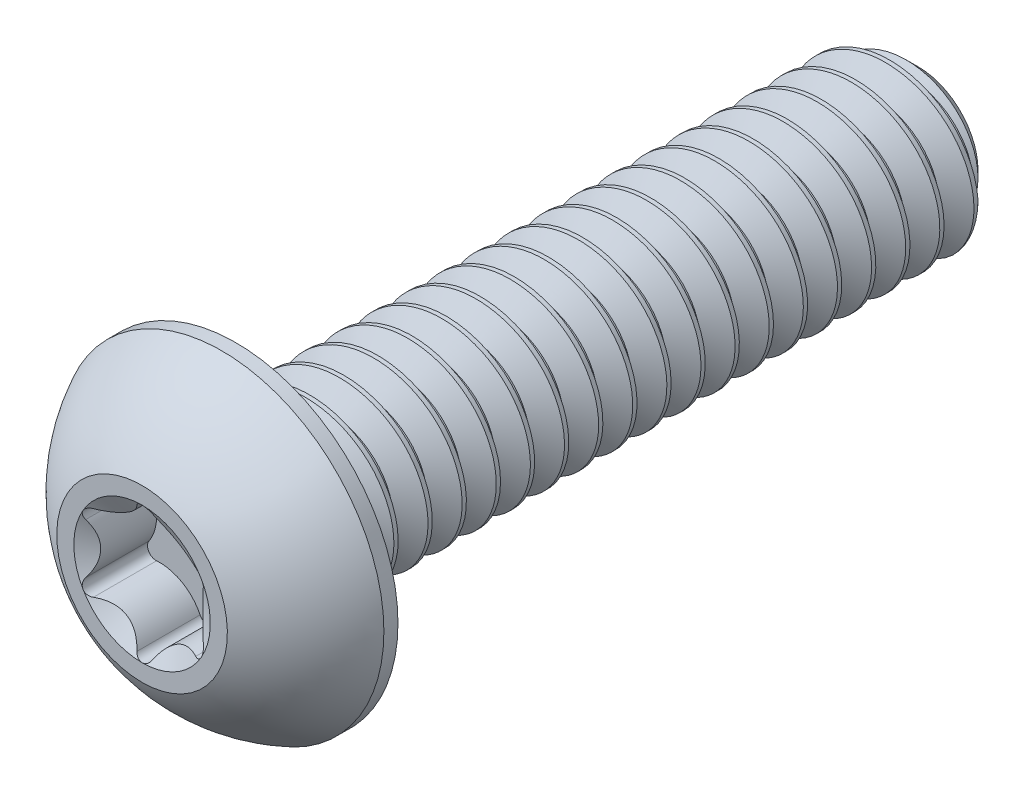
SolidWorks part; units mm, degrees
ref_plane "Front" through (0, 0, 0) normal (0, 0, 1) x (1, 0, 0)
ref_plane "Top" through (0, 0, 0) normal (0, 1, 0) x (1, 0, 0)
ref_plane "Right" through (0, 0, 0) normal (1, 0, 0) x (0, 0, -1)
sketch "Sketch1" plane through (0, 0, 0) normal (1, 0, 0) x (0, 0, -1)
  line L2 (1.1, 1) -> (9.1, 1)
  line L3 (9.1, 1) -> (9.1, 0)
  line L4 (9.1, 0) -> (1.1, 0)
  line L6 (0.935, 1.9) -> (1.1, 1.9) construction
  line L7 (9.1, 1) -> (9.1, -1) construction
  line L8 (0, 0) -> (1.1, 0) construction
  line L9 (1.1, 1.9) -> (1.1, -1.9) construction
  line L11 (1.1, 1) -> (1.1, 0)
  line L14 (0, 0) -> (0, 1) construction
  arc A3 (0, 1) -> (0.935, 1.9) centre (1.8632, 0) cw construction
  dimension "D1" = 0.165
revolve "Revolve1" add sketch "Sketch1" angle 360 mid plane about L4
sketch "Sketch3" plane through (0, 0, -9.1) normal (0, 0, -1) x (-1, 0, 0)
  circle A0 centre (0, 0) radius 1
curve "Helix/Spiral1" pitch 0.4 height 8.4 radius 1 centre (0, 0, -9.1) axis (0, 0, 1) start towards (0, 1, 0)
sketch "Sketch2" plane through (0, 0, 0) normal (1, 0, 0) x (0, 0, -1)
  line L0 (9.1, 1) -> (9.45, 1)
  line L1 (9.45, 1) -> (9.3, 0.7402)
  line L2 (9.3, 0.7402) -> (9.25, 0.7402)
  line L3 (9.25, 0.7402) -> (9.1, 1)
  line L4 (9.175, 0.8701) -> (9.375, 0.8701) construction
  dimension "D1" = 60
  dimension "D2" = 0.05
  dimension "D3" = 0.2
chamfer "Chamfer1" distance 0.3 angle 45 1 edges at (0, 1, -9.1)
sweep "Cut-Sweep1" cut profiles "Sketch2" path "Helix/Spiral1" align with end faces yes
sketch "Sketch7" plane through (0, 0, 0) normal (1, 0, 0) x (0, 0, -1)
  line L0 (0, 0) -> (0, 1) construction
  line L6 (0.935, 1.9) -> (1.1, 1.9) construction
  line L8 (0, 0) -> (1.1, 0) construction
  line L11 (1.1, 1.9) -> (1.1, -1.9) construction
  line L12 (0.935, 1.9) -> (1.1, 1.9)
  line L13 (0, 0) -> (1.1, 0)
  line L15 (1.1, 1.9) -> (1.1, 0)
  line L16 (0, 1) -> (0, 0)
  arc A2 (0.935, 1.9) -> (0, 1) centre (1.8632, 0) ccw construction
  arc A3 (0.935, 1.9) -> (0, 1) centre (1.8632, 0) ccw
revolve "Revolve2" add sketch "Sketch7" angle 360 mid plane about L13
sketch "Sketch5" plane through (0, 0, 0) normal (0, 0, 1) x (1, 0, 0)
  line L0 (2.6125, 0) -> (-2.6125, 0) construction
  line L2 (0, 0) -> (-0.6928, 0.4)
  line L3 (0, 0) -> (-0.6928, -0.4)
  line L4 (0, 0.8) -> (0, 0.7) construction
  line L5 (0, 0.7) -> (0, 0.6) construction
  circle A0 centre (0, 0) radius 0.6 construction
  circle A1 centre (0, 0) radius 0.7 construction
  circle A2 centre (0, 0) radius 0.8 construction
  arc A3 (-0.6894, 0.2944) -> (-0.6894, -0.2944) centre (-1.1298, 0) cw
  arc A4 (-0.6894, 0.2944) -> (-0.6928, 0.4) centre (-0.6062, 0.35) cw
  arc A5 (-0.6894, -0.2944) -> (-0.6928, -0.4) centre (-0.6062, -0.35) ccw
  dimension "D4" = 1.2
  dimension "D2" = 1.6
  dimension "D1" = 30
extrude "Cut-Extrude2" cut sketch "Sketch5" against normal blind 0.77
pattern_circular "CirPattern1" count 6 over 360 of "Cut-Extrude2"
sketch "Sketch11" plane through (0, 0, 0) normal (0, 0, 1) x (1, 0, 0)
  circle A0 centre (0, 0) radius 0.8 construction
  circle A1 centre (0, 0) radius 0.8
extrude "Cut-Extrude3" cut sketch "Sketch11" against normal blind 0.77 draft 60
sketch "Sketch9" [suppressed] plane through (0, 0, -1.4986) normal (0, 0, 1) x (1, 0, 0)
  circle A2 centre (0, 0) radius 1.4224
extrude "Boss-Extrude2" [suppressed] add sketch "Sketch9" against normal offset from surface (7.0104 mm away) 31.75 up to face at (0, 0.7, -9.1)
sketch "Sketch10" plane through (0, 0, 0) normal (1, 0, 0) x (0, 0, -1)
  line L0 (9.1, 1) -> (9.1, -1) construction
  point P0 (8.5, -1)
  dimension "D1" = 0.6
equation "\"D3@Helix/Spiral1\" = \"Lg@Sketch1\" + \"D4@Helix/Spiral1\""
equation "\"D2@Sketch2\" = \"D4@Helix/Spiral1\" * .125"
equation "\"D3@Sketch2\" = \"D4@Helix/Spiral1\" * .5"
equation "\"D1@Chamfer1\" = \"D4@Helix/Spiral1\" * .75"
equation "\"D1@Cut-Extrude2\" = \"Head Ht@Sketch1\" * .7"
equation "\"D1@Sketch1\" = \"Head Ht@Sketch1\" * .15"
equation "\"D1@Sketch10\" = \"D4@Helix/Spiral1\" * 1.5"
equation "\"D1@Cut-Extrude3\" = \"D1@Cut-Extrude2\""
equation "\"D2@Sketch5\" = \"Dia@Sketch1\" * .8"
equation "\"D4@Sketch5\" = \"D2@Sketch5\" * .75"
